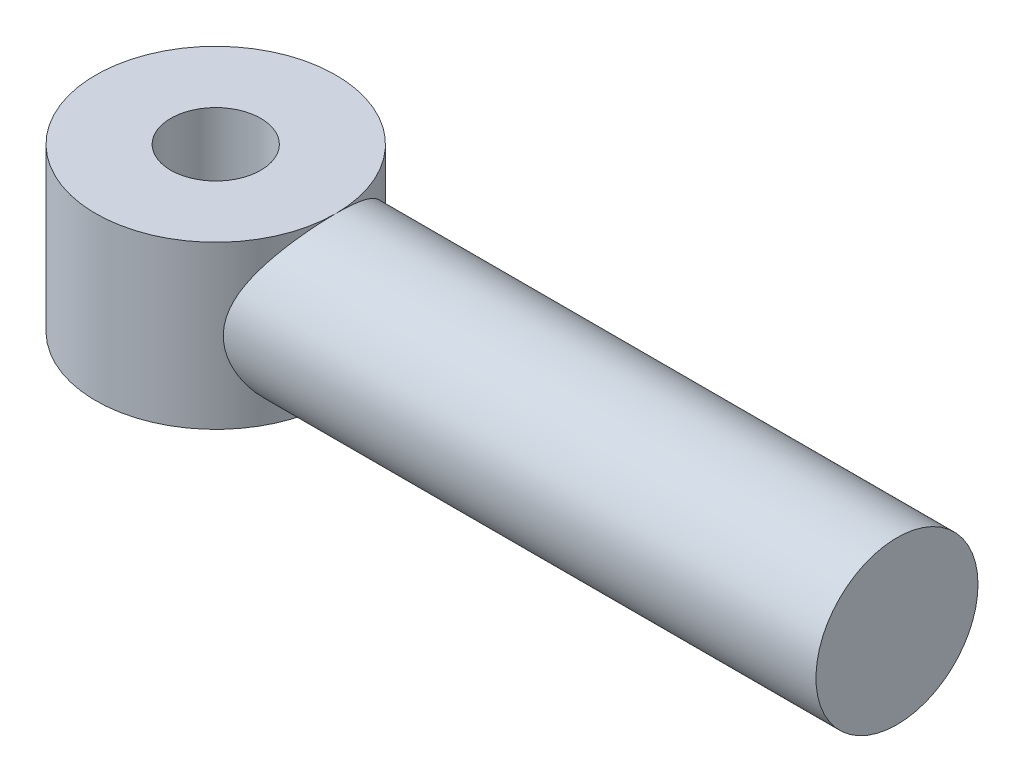
SolidWorks part; units mm, degrees
ref_plane "Front Plane" through (0, 0, 0) normal (0, 0, 1) x (1, 0, 0)
ref_plane "Top Plane" through (0, 0, 0) normal (0, 1, 0) x (1, 0, 0)
ref_plane "Right Plane" through (0, 0, 0) normal (1, 0, 0) x (0, 0, -1)
sketch "Sketch1" plane through (0, 0, 0) normal (1, 0, 0) x (0, 0, -1)
  circle A0 centre (0, 0) radius 1.35
  dimension "D1" = 2.7
extrude "Boss-Extrude1" add sketch "Sketch1" along normal blind 11.35
sketch "Sketch2" plane through (0, 0, 0) normal (0, 1, 0) x (1, 0, 0)
  line L0 (0, 1.35) -> (0, -1.35) construction
  circle A0 centre (0, 0) radius 2
  dimension "D1" = 4
extrude "Boss-Extrude2" add sketch "Sketch2" along normal blind 1.35 and the other way blind 1.35
sketch "Sketch3" plane through (0, 1.35, 0) normal (0, 1, 0) x (1, 0, 0)
  circle A0 centre (0, 0) radius 0.75
  dimension "D1" = 1.5
extrude "Cut-Extrude1" cut sketch "Sketch3" against normal blind 11.35
